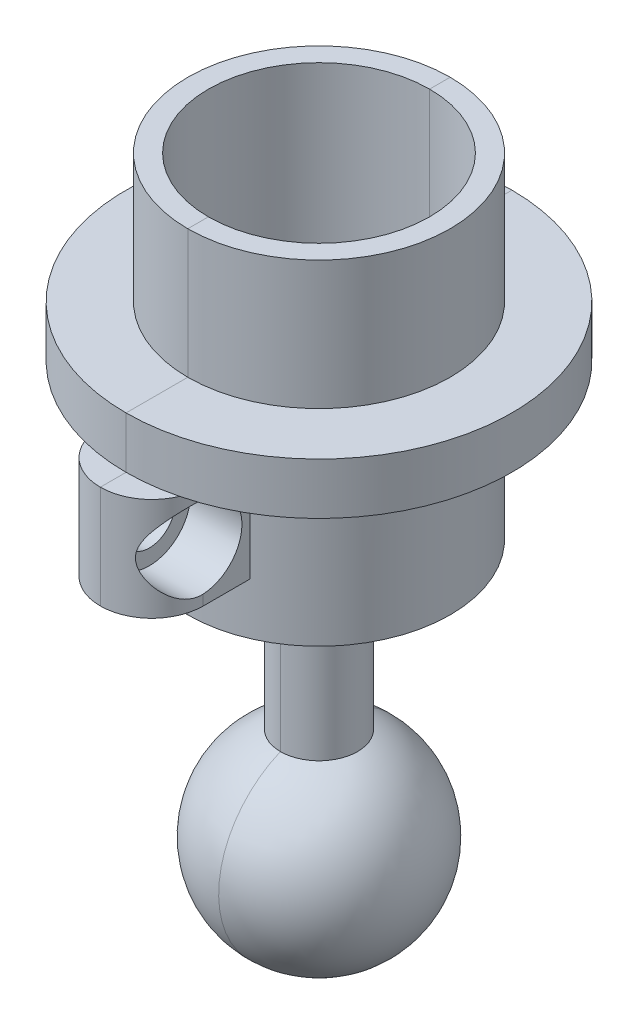
SolidWorks part; units mm, degrees
ref_plane "Front Plane" through (0, 0, 0) normal (0, 0, 1) x (1, 0, 0)
ref_plane "Top Plane" through (0, 0, 0) normal (0, 1, 0) x (1, 0, 0)
ref_plane "Right Plane" through (0, 0, 0) normal (1, 0, 0) x (0, 0, -1)
sketch "Sketch2" plane through (0, 0, 0) normal (0, 1, 0) x (1, 0, 0)
  circle A0 centre (0, 0) radius 5.1
  dimension "D1" = 10.2
extrude "Boss-Extrude1" add sketch "Sketch2" along normal blind 1
sketch "Sketch3" plane through (0, 1, 0) normal (0, 1, 0) x (1, 0, 0)
  circle A0 centre (0, 0) radius 5.1
  circle A1 centre (0, 0) radius 4.3
  circle M1 centre (0, 0) radius 5.1
  dimension "D1" = 10.2
  dimension "D2" = 8.6
extrude "Boss-Extrude2" add sketch "Sketch3" along normal blind 12 contours A1 M1 region at (-4.9558, 1, 0)
sketch "Sketch6" plane through (0, 1, 0) normal (0, 1, 0) x (1, 0, 0)
  line L0 (0, 0) -> (0, 3.3)
  line L1 (0, 0) -> (-0.8541, 3.1876) construction
  line L2 (0, 0) -> (0.8541, 3.1876) construction
  line L3 (0.8541, 3.1876) -> (0.647, 2.4148)
  line L4 (-0.8541, 3.1876) -> (-0.647, 2.4148)
  line L5 (3.1876, 0.8541) -> (2.4148, 0.647)
  line L6 (2.3335, 2.3335) -> (1.7678, 1.7678)
  line L7 (2.3335, -2.3335) -> (1.7678, -1.7678)
  line L8 (3.1876, -0.8541) -> (2.4148, -0.647)
  line L9 (-0.8541, -3.1876) -> (-0.647, -2.4148)
  line L10 (0.8541, -3.1876) -> (0.647, -2.4148)
  line L11 (-3.1876, -0.8541) -> (-2.4148, -0.647)
  line L12 (-2.3335, -2.3335) -> (-1.7678, -1.7678)
  line L13 (-2.3335, 2.3335) -> (-1.7678, 1.7678)
  line L14 (-3.1876, 0.8541) -> (-2.4148, 0.647)
  arc A0 (0.8541, 3.1876) -> (-0.8541, 3.1876) centre (0, 0) ccw
  arc A1 (0.647, 2.4148) -> (-0.647, 2.4148) centre (0, 0) ccw
  arc A2 (3.1876, 0.8541) -> (2.3335, 2.3335) centre (0, 0) ccw
  arc A3 (2.4148, 0.647) -> (1.7678, 1.7678) centre (0, 0) ccw
  arc A4 (2.3335, -2.3335) -> (3.1876, -0.8541) centre (0, 0) ccw
  arc A5 (1.7678, -1.7678) -> (2.4148, -0.647) centre (0, 0) ccw
  arc A6 (-0.8541, -3.1876) -> (0.8541, -3.1876) centre (0, 0) ccw
  arc A7 (-0.647, -2.4148) -> (0.647, -2.4148) centre (0, 0) ccw
  arc A8 (-3.1876, -0.8541) -> (-2.3335, -2.3335) centre (0, 0) ccw
  arc A9 (-2.4148, -0.647) -> (-1.7678, -1.7678) centre (0, 0) ccw
  arc A10 (-2.3335, 2.3335) -> (-3.1876, 0.8541) centre (0, 0) ccw
  arc A11 (-1.7678, 1.7678) -> (-2.4148, 0.647) centre (0, 0) ccw
  point P29 (0, 0)
  dimension "D1" = 6.6
  dimension "D2" = 5
  dimension "D3" = 15
  dimension "D4" = 15
  dimension "D5" = 6
extrude "Cut-Extrude2" cut sketch "Sketch6" against normal blind 1 contours A11 L13 A10 L14 | A3 L5 A2 L6 | A5 L7 A4 L8 | A7 L9 A6 L10 | A9 L11 A8 L12 | A1 L4 A0 L3 region at (2.4986, 1, -1.4426) region at (2.4986, 1, 1.4426) region at (0, 1, 2.8852) region at (-2.4986, 1, 1.4426) region at (-2.4986, 1, -1.4426)
ref_plane "Plane2" through (0, 6, 0) normal (0, 1, 0) x (1, 0, 0)
sketch "Sketch7" plane through (0, 6, 0) normal (0, 1, 0) x (1, 0, 0)
  circle A0 centre (0, 0) radius 7.5
  circle A1 centre (0, 0) radius 5.1
  dimension "D1" = 15
  dimension "D2" = 10.2
extrude "Boss-Extrude4" add sketch "Sketch7" along normal blind 2
sketch "Sketch8" plane through (0, 0, 0) normal (1, 0, 0) x (0, 0, -1)
  line L0 (0, 0) -> (0, -10)
  line L1 (1.5, -6.4) -> (1.5, 0)
  line L2 (-1.5, 0) -> (-1.5, -6.4)
  line L3 (-5.1, 0) -> (5.1, 0) construction
  line L5 (0.8541, 0) -> (2.3335, 0) construction
  line L6 (1.5, 0) -> (-1.5, 0)
  line L7 (0, -10) -> (0, -13.9)
  circle A0 centre (0, -10) radius 3.9
  dimension "D2" = 7.8
  dimension "D1" = 10
  dimension "D3" = 3
revolve "Revolve1" add sketch "Sketch8" angle 360 about L0 region at (0, -3.0998, 0.756) region at (0, -10, 1.6552)
ref_plane "Plane3" through (0, 0, 8.5) normal (0, 0, 1) x (1, 0, 0)
sketch "Sketch11" plane through (0, 0, 8.5) normal (0, 0, 1) x (1, 0, 0)
  line L0 (0, 6) -> (0, 0) construction
  line L1 (8.25, 6) -> (-8.25, 6) construction
  line L3 (-2, 2) -> (2, 2)
  line L4 (-2, 2) -> (-2, 6)
  line L5 (-2, 6) -> (2, 6)
  line L6 (2, 2) -> (2, 6)
  line L7 (-2, 2) -> (2, 6) construction
  line L8 (-2, 6) -> (2, 2) construction
  point P5 (0, 4)
  point P10 (0, 3.8974)
  dimension "D1" = 4
  dimension "D2" = 4
extrude "Boss-Extrude5" add sketch "Sketch11" against normal up to next
sketch "Sketch13" plane through (2, 0, 0) normal (1, 0, 0) x (0, 0, -1)
  line L0 (-4.6915, 2) -> (-8.5, 6) construction
  line L1 (-8.5, 8.25) -> (-8.5, -8.25) construction
  line L2 (8.25, 6) -> (-8.25, 6) construction
  circle A0 centre (-6.5957, 4) radius 1
  circle A1 centre (-6.5957, 4) radius 1.6
  dimension "D1" = 2
  dimension "D2" = 3.2
extrude "Cut-Extrude3" cut sketch "Sketch13" against normal blind 10 contours L0 A0 | A0 L0 region at (2, 3.7073, 6.9031) region at (2, 4.2927, 6.2884)
extrude "Cut-Extrude4" cut sketch "Sketch13<3>" against normal blind 2
sketch "Sketch13<3>" plane through (2, 0, 0) normal (1, 0, 0) x (0, 0, -1) same geometry as "Sketch13"
fillet "Fillet1" radius 2 2 edges at (-2, 4, 8.5) (2, 4, 8.5)
mirror "Mirror1" about plane through (0, 0, 0) normal (0, 0, 1) of "Boss-Extrude5", "Cut-Extrude3", "Cut-Extrude4", "Fillet1"
split "Split1" trim tools "Right Plane" bodies to split 112 resulting bodies 113 114
